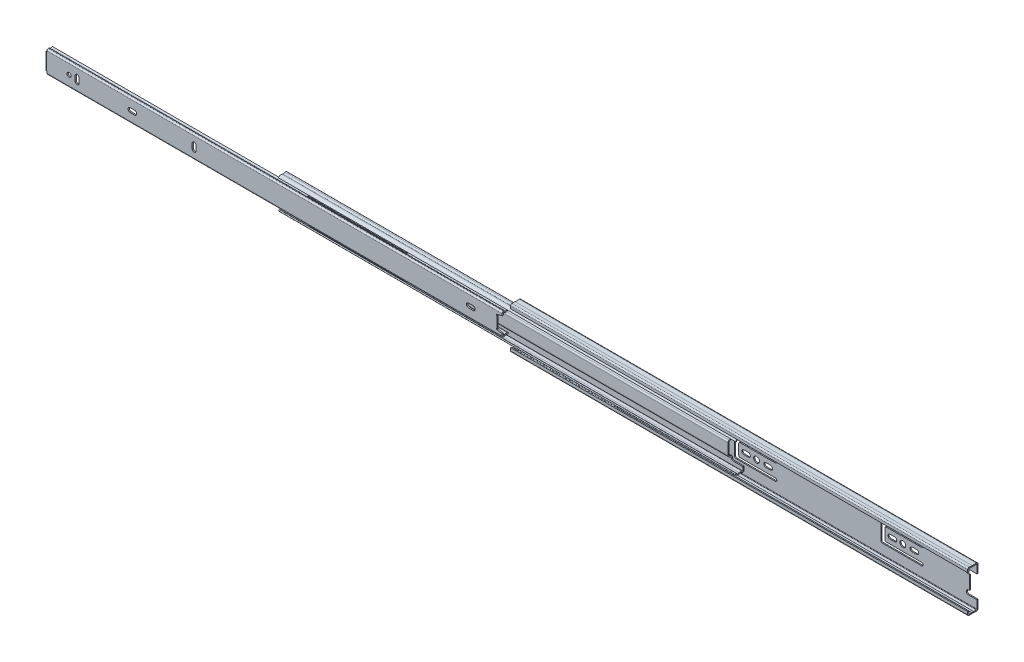
SolidWorks part; units mm, degrees
ref_plane "Front" through (0, 0, 0) normal (0, 0, 1) x (1, 0, 0)
ref_plane "Top" through (0, 0, 0) normal (0, 1, 0) x (1, 0, 0)
ref_plane "Right" through (0, 0, 0) normal (1, 0, 0) x (0, 0, -1)
sketch "Sketch1" plane through (0, 0, 0) normal (1, 0, 0) x (0, 0, -1)
  line L1 (5.6388, 0) -> (-5.6388, 0) construction
  line L4 (-4.1393, 22.8203) -> (-0.7433, 22.6989)
  line L5 (-1.1312, 21.5182) -> (-4.1819, 21.6273)
  line L6 (-4.445, 18.415) -> (-5.6388, 18.415)
  line L7 (-4.445, 21.3734) -> (-4.445, 18.415)
  line L8 (-5.6388, 18.415) -> (-5.6388, 21.3734)
  line L9 (3.9237, 21.6269) -> (0.7619, 21.5441)
  line L10 (5.6388, 0) -> (5.6388, 21.1191)
  line L11 (4.445, 21.1191) -> (4.445, 0)
  line L12 (5.6388, 0) -> (4.445, 0)
  line L13 (-0.7433, 22.6989) -> (3.8925, 22.8203)
  arc A0 (-4.445, 21.3734) -> (-4.1819, 21.6273) centre (-4.191, 21.3734) cw
  arc A1 (-5.6388, 21.3734) -> (-4.1393, 22.8203) centre (-4.191, 21.3734) cw
  arc A3 (3.9237, 21.6269) -> (4.445, 21.1191) centre (3.937, 21.1191) cw
  arc A4 (3.8925, 22.8203) -> (5.6388, 21.1191) centre (3.937, 21.1191) cw
  arc A5 (-1.1312, 21.5182) -> (0.7619, 21.5441) centre (-0.1524, 19.1744) cw
  dimension "D2" = 19.1744
  dimension "D7" = 0.254
  dimension "D8" = 0.508
  dimension "D6" = 2.54
  dimension "D9" = 1.1938
  dimension "D10" = 88.5
  dimension "D1" = 11.2776
  dimension "D3" = 5.7912
  dimension "D4" = 36.83
  dimension "D5" = 1.1938
  dimension "D11" = 87.953
  dimension "D12" = 45.6406
extrude "Extrude1" add sketch "Sketch1" along normal mid plane 500.126
ref_plane "Travel / 2" through (-504.063, 0, 0) normal (-1, 0, 0) x (0, 0, 1)
sketch "Sketch2" plane through (-504.063, 0, 0) normal (-1, 0, 0) x (0, 0, 1)
  line L0 (0.0254, 6.1159) -> (0.0254, 0)
  line L2 (-5.6388, 0) -> (5.6388, 0) construction
  line L3 (5.6388, 21.3734) -> (5.6388, 18.415) construction
  line L7 (-4.445, 21.1191) -> (-4.445, 0) construction
  line L8 (-5.6388, 0) -> (-5.6388, 21.1191) construction
  line L13 (-3.5306, 16.3766) -> (-3.5306, 9.5217)
  line L46 (-2.3867, 7.7262) -> (-0.4146, 6.8065)
  arc A0 (0.0254, 6.1159) -> (-0.4146, 6.8065) centre (-0.7366, 6.1159) ccw
  arc A1 (-1.5056, 17.2916) -> (1.2415, 16.9143) centre (0.1524, 19.1744) ccw
  arc A4 (1.1312, 21.5182) -> (-0.7619, 21.5441) centre (0.1524, 19.1744) ccw construction
  arc A19 (-3.5306, 9.5217) -> (-2.3867, 7.7262) centre (-1.5494, 9.5217) ccw
  arc A25 (-1.5056, 17.2916) -> (-3.5306, 16.3766) centre (-2.3114, 16.3766) ccw
  arc A51 (5.7404, 15.6277) -> (1.2415, 16.9143) centre (2.7686, 13.7451) ccw
  dimension "D2" = 8.4074
  dimension "D3" = 27.4903
  dimension "D6" = 1.9812
  dimension "D8" = 12.2319
  dimension "D10" = 2.5088
  dimension "D11" = 1.2192
  dimension "D4" = 0.762
  dimension "D5" = 4.4704
  dimension "D7" = 115
  dimension "D9" = 19.0435
  dimension "D13" = 11.3792
extrude "Middle Member" add sketch "Sketch2" against normal blind 500.126 separate body thin thin type one direction reverse wall 1.2192
ref_plane "Travel" through (-758.063, 0, 0) normal (-1, 0, 0) x (0, 0, 1)
sketch "Sketch3" plane through (-758.063, 0, 0) normal (-1, 0, 0) x (0, 0, 1)
  line L0 (1.2446, 0) -> (0.0254, 0) construction
  line L1 (-5.6388, 0) -> (-5.6388, 21.1191) construction
  line L56 (7.0612, 0) -> (7.0612, 10.6235)
  line L93 (5.5372, 12.1475) -> (5.1643, 12.1475)
  arc A0 (1.2082, 11.9072) -> (4.2365, 11.8325) centre (2.7686, 13.7451) ccw
  arc A29 (7.0612, 10.6235) -> (5.5372, 12.1475) centre (5.5372, 10.6235) ccw
  arc A53 (5.1643, 12.1475) -> (4.2365, 11.8325) centre (5.1643, 10.6235) ccw
  dimension "D1" = 1.524
  dimension "D4" = 1.524
  dimension "D5" = 2.411
  dimension "D2" = 12.7
  dimension "D3" = 12.1475
  dimension "D6" = 5.853
extrude "Drawer Member" add sketch "Sketch3" against normal blind 500.126 thin thin type one direction wall 1.397
sketch "Sketch6" plane through (0, 0, 7.0612) normal (0, 0, 1) x (1, 0, 0)
  line L1 (-758.063, 0) -> (-756.158, 0)
  line L2 (-758.063, 0) -> (-758.063, 12.1475)
  line L3 (-758.063, 12.1475) -> (-756.158, 12.1475)
  line L4 (-756.158, 0) -> (-756.158, 12.1475)
  line L5 (-257.937, 12.1475) -> (-758.063, 12.1475) construction
  line L7 (-758.063, 10.6235) -> (-758.063, 0) construction
  line L8 (-257.937, 0) -> (-758.063, 0) construction
  dimension "D1" = 1.905
extrude "Cut-Extrude1" cut sketch "Sketch6" against normal through all
sketch "Sketch7" plane through (0, 0, 0) normal (0, -1, 0) x (1, 0, 0)
  line L0 (-756.158, 7.0612) -> (-756.412, 7.0612)
  line L1 (-758.063, 5.4102) -> (-758.063, 0.3041)
  line L2 (-758.063, 0.3041) -> (-756.666, 0.3041)
  line L3 (-756.666, 0.3041) -> (-756.666, 5.4102)
  line L4 (-756.412, 5.6642) -> (-756.158, 5.6642)
  line L5 (-257.937, 5.6642) -> (-756.158, 5.6642) construction
  line L6 (-756.158, 7.0612) -> (-756.158, 5.6642)
  line L7 (-257.937, 0.3041) -> (-756.158, 0.3041) construction
  line L9 (-756.158, 5.087) -> (-756.158, 0.3041) construction
  arc A0 (-756.412, 5.6642) -> (-756.666, 5.4102) centre (-756.412, 5.4102) ccw
  arc A1 (-756.412, 7.0612) -> (-758.063, 5.4102) centre (-756.412, 5.4102) ccw
  dimension "D1" = 0.254
  dimension "D2" = 1.905
extrude "Extrude4" add sketch "Sketch7" against normal blind 8.89
sketch "Sketch8" plane through (0, 0, -4.445) normal (0, 0, 1) x (1, 0, 0)
  line L0 (240.4245, 7.6456) -> (241.8588, 7.493)
  line L1 (250.063, 12.2048) -> (240.6664, 12.2048)
  line L2 (241.8588, 7.493) -> (241.8588, 0)
  line L3 (250.063, 0) -> (-250.063, 0) construction
  line L4 (250.063, 21.1191) -> (250.063, 0) construction
  line L5 (250.063, 12.2048) -> (250.063, 0)
  line L6 (250.063, 0) -> (241.8588, 0)
  arc A0 (240.6664, 12.2048) -> (240.4245, 7.6456) centre (240.6664, 9.9188) ccw
  dimension "D3" = 9.9188
  dimension "D1" = 12.2048
  dimension "D2" = 8.2042
  dimension "D4" = 9.3966
  dimension "D5" = 7.493
extrude "Cut-Extrude2" cut sketch "Sketch8" against normal up to next (1.1938 mm away)
sketch "Sketch11" plane through (0, 0, 7.0612) normal (0, 0, 1) x (1, 0, 0)
  line L0 (-263.652, 5.9678) -> (-263.652, 0)
  line L8 (-257.937, 8.5893) -> (-263.7963, 7.2212)
  line L11 (-263.652, 0) -> (-257.937, 0)
  line L12 (-257.937, 0) -> (-257.937, 8.5893)
  arc A1 (-263.7963, 7.2212) -> (-263.652, 5.9678) centre (-263.6519, 6.6028) ccw
  dimension "D3" = 0.635
  dimension "D1" = 5.715
  dimension "D2" = 8.5893
  dimension "D4" = 5.9678
  dimension "D5" = 103.143
extrude "Cut-Extrude3" cut sketch "Sketch11" against normal up to next (1.397 mm away)
sketch "Sketch12" plane through (0, 0, 1.2446) normal (0, 0, 1) x (1, 0, 0)
  line L0 (-3.937, 12.065) -> (-14.097, 12.065)
  line L1 (-3.937, 16.3766) -> (-3.937, 9.5217) construction
  line L2 (-16.637, 9.525) -> (-16.637, 0)
  line L3 (-3.937, 0) -> (-504.063, 0) construction
  line L4 (-16.637, 0) -> (-3.937, 0)
  line L5 (-3.937, 0) -> (-3.937, 12.065)
  arc A0 (-14.097, 12.065) -> (-16.637, 9.525) centre (-14.097, 9.525) ccw
  point P11 (-16.637, 12.065)
  dimension "D3" = 2.54
  dimension "D1" = 12.7
  dimension "D2" = 12.065
extrude "Cut-Extrude4" cut sketch "Sketch12" against normal through all
sketch "Sketch13" plane through (0, 0, -4.445) normal (0, 0, 1) x (1, 0, 0)
  line L0 (-181.6747, 7.112) -> (-206.5032, 7.112)
  line L1 (241.8588, 0) -> (-250.063, 0) construction
  line L2 (-189.7646, 0) -> (-189.7646, 4.2392) construction
  line L3 (-232.6017, 10.287) -> (-181.6747, 10.287)
  line L4 (-250.063, 21.1191) -> (-250.063, 0) construction
  line L5 (-210.3132, 7.112) -> (-232.6017, 7.112)
  line L6 (-209.5512, 0) -> (-209.5512, 6.35)
  line L7 (-207.2652, 6.35) -> (-207.2652, 0)
  line L8 (-187.2881, 2.286) -> (-192.2411, 2.286)
  line L13 (-226.3406, 0) -> (-221.7686, 0)
  line L14 (-218.238, 0) -> (-211.888, 0)
  line L15 (-209.5512, 0) -> (-207.2652, 0)
  line L16 (-204.7506, 0) -> (-200.1786, 0)
  line L17 (-194.5271, 0) -> (-185.0021, 0)
  arc A1 (-232.6017, 10.287) -> (-232.6017, 7.112) centre (-232.6017, 8.6995) ccw
  arc A2 (-209.5512, 6.35) -> (-210.3132, 7.112) centre (-210.3132, 6.35) ccw
  arc A4 (-206.5032, 7.112) -> (-207.2652, 6.35) centre (-206.5032, 6.35) ccw
  arc A7 (-181.6747, 7.112) -> (-181.6747, 10.287) centre (-181.6747, 8.6995) ccw
  arc A8 (-211.888, 0) -> (-218.238, 0) centre (-215.063, 0) ccw
  arc A9 (-221.7686, 0) -> (-226.3406, 0) centre (-224.0546, 0) ccw
  arc A10 (-200.1786, 0) -> (-204.7506, 0) centre (-202.4646, 0) ccw
  arc A11 (-185.0021, 0) -> (-187.2881, 2.286) centre (-187.2881, 0) ccw
  arc A12 (-192.2411, 2.286) -> (-194.5271, 0) centre (-192.2411, 0) ccw
  dimension "D3" = 2.286
  dimension "D4" = 3.175
  dimension "D7" = 8.9916
  dimension "D8" = 21.59
  dimension "D9" = 34.29
  dimension "D10" = 0.762
  dimension "D11" = 17.5387
  dimension "D12" = 9.525
  dimension "D13" = 5.5118
  dimension "D14" = 35
  dimension "D1" = 3.175
  dimension "D2" = 50.927
  dimension "D5" = 2.286
  dimension "D6" = 10.287
extrude "Cut-Extrude5" cut sketch "Sketch13" against normal up to next (1.1938 mm away)
sketch "Sketch32" plane through (0, 0, -5.6388) normal (0, 0, -1) x (-1, 0, 0)
  line L0 (69.6005, 0) -> (79.1255, 0)
  line L1 (83.888, 0) -> (90.238, 0)
  line L2 (93.7305, 0) -> (103.2555, 0)
  line L3 (106.621, 0) -> (111.193, 0)
  line L4 (-241.8588, 0) -> (185.0021, 0) construction
  line L5 (232.6017, 10.287) -> (181.6747, 10.287) construction
  line L6 (181.6747, 7.112) -> (206.5032, 7.112) construction
  line L7 (98.493, 2.286) -> (98.493, -3.4269) construction
  line L8 (74.363, 2.286) -> (74.363, -3.4269) construction
  line L14 (66.4255, 10.287) -> (109.669, 10.287)
  line L15 (105.097, 7.112) -> (66.4255, 7.112)
  line L17 (111.193, 8.763) -> (111.193, 0)
  line L18 (106.621, 0) -> (106.621, 5.588)
  line L23 (71.8865, 2.286) -> (76.8395, 2.286)
  line L25 (96.0165, 2.286) -> (100.9695, 2.286)
  arc A0 (218.238, 0) -> (211.888, 0) centre (215.063, 0) ccw construction
  arc A13 (111.193, 8.763) -> (109.669, 10.287) centre (109.669, 8.763) ccw
  arc A14 (106.621, 5.588) -> (105.097, 7.112) centre (105.097, 5.588) ccw
  arc A17 (66.4255, 10.287) -> (66.4255, 7.112) centre (66.4255, 8.6995) ccw
  arc A20 (79.1255, 0) -> (76.8395, 2.286) centre (76.8395, 0) ccw
  arc A21 (71.8865, 2.286) -> (69.6005, 0) centre (71.8865, 0) ccw
  arc A22 (90.238, 0) -> (83.888, 0) centre (87.063, 0) ccw
  arc A24 (103.2555, 0) -> (100.9695, 2.286) centre (100.9695, 0) ccw
  arc A25 (96.0165, 2.286) -> (93.7305, 0) centre (96.0165, 0) ccw
  dimension "D2" = 1.524
  dimension "D3" = 3.175
  dimension "D4" = 9.525
  dimension "D5" = 2.286
  dimension "D6" = 11.43
  dimension "D7" = 12.7
  dimension "D8" = 24.13
  dimension "D9" = 20.6375
  dimension "D10" = 128
  dimension "D1" = 4.572
extrude "Cut-Extrude14" cut sketch "Sketch32" against normal up to next (1.1938 mm away)
sketch "Sketch33" plane through (83.6094, 0.8125, -5.6388) normal (0, 0, -1) x (-1, 0, 0)
  line L0 (57.2099, -0.8125) -> (66.7349, -0.8125)
  line L1 (71.4974, -0.8125) -> (77.8474, -0.8125)
  line L2 (81.3399, -0.8125) -> (90.8649, -0.8125)
  line L3 (94.2304, -0.8125) -> (98.8024, -0.8125)
  line L7 (86.1024, 1.4735) -> (86.1024, -4.2394) construction
  line L8 (61.9724, 1.4735) -> (61.9724, -3.4269) construction
  line L9 (-158.2494, -0.8125) -> (153.2099, -0.8125) construction
  line L10 (193.2784, 9.4745) -> (150.0349, 9.4745) construction
  line L11 (150.0349, 6.2995) -> (188.7064, 6.2995) construction
  line L14 (54.0349, 9.4745) -> (97.2784, 9.4745)
  line L15 (92.7064, 6.2995) -> (54.0349, 6.2995)
  line L17 (98.8024, 7.9505) -> (98.8024, -0.8125)
  line L18 (94.2304, -0.8125) -> (94.2304, 4.7755)
  line L23 (59.4959, 1.4735) -> (64.4489, 1.4735)
  line L25 (83.6259, 1.4735) -> (88.5789, 1.4735)
  arc A1 (301.8474, -0.8125) -> (295.4974, -0.8125) centre (298.6724, -0.8125) ccw construction
  arc A13 (98.8024, 7.9505) -> (97.2784, 9.4745) centre (97.2784, 7.9505) ccw
  arc A14 (94.2304, 4.7755) -> (92.7064, 6.2995) centre (92.7064, 4.7755) ccw
  arc A17 (54.0349, 9.4745) -> (54.0349, 6.2995) centre (54.0349, 7.887) ccw
  arc A20 (66.7349, -0.8125) -> (64.4489, 1.4735) centre (64.4489, -0.8125) ccw
  arc A21 (59.4959, 1.4735) -> (57.2099, -0.8125) centre (59.4959, -0.8125) ccw
  arc A22 (77.8474, -0.8125) -> (71.4974, -0.8125) centre (74.6724, -0.8125) ccw
  arc A24 (90.8649, -0.8125) -> (88.5789, 1.4735) centre (88.5789, -0.8125) ccw
  arc A25 (83.6259, 1.4735) -> (81.3399, -0.8125) centre (83.6259, -0.8125) ccw
  dimension "D2" = 1.524
  dimension "D3" = 3.175
  dimension "D4" = 9.525
  dimension "D5" = 2.286
  dimension "D6" = 11.43
  dimension "D7" = 12.7
  dimension "D8" = 24.13
  dimension "D9" = 20.6375
  dimension "D10" = 224
  dimension "D1" = 4.572
extrude "Cut-Extrude6" cut sketch "Sketch33" against normal up to next (1.1938 mm away)
sketch "Sketch34" plane through (169.8236, 1.4527, -5.6388) normal (0, 0, -1) x (-1, 0, 0)
  line L0 (-16.6239, -1.4527) -> (-7.0989, -1.4527)
  line L1 (-2.3364, -1.4527) -> (4.0136, -1.4527)
  line L2 (7.5061, -1.4527) -> (17.0311, -1.4527)
  line L3 (20.3966, -1.4527) -> (24.9686, -1.4527)
  line L4 (-72.0352, -1.4527) -> (143.4241, -1.4527) construction
  line L7 (12.2686, 0.8333) -> (12.2686, -4.8796) construction
  line L8 (-11.8614, 0.8333) -> (-11.8614, -4.0671) construction
  line L9 (279.4926, 8.8343) -> (236.2491, 8.8343) construction
  line L10 (236.2491, 5.6593) -> (274.9206, 5.6593) construction
  line L14 (-19.7989, 8.8343) -> (23.4446, 8.8343)
  line L15 (18.8726, 5.6593) -> (-19.7989, 5.6593)
  line L17 (24.9686, 7.3103) -> (24.9686, -1.4527)
  line L18 (20.3966, -1.4527) -> (20.3966, 4.1353)
  line L23 (-14.3379, 0.8333) -> (-9.3849, 0.8333)
  line L25 (9.7921, 0.8333) -> (14.7451, 0.8333)
  arc A0 (388.0616, -1.4527) -> (381.7116, -1.4527) centre (384.8866, -1.4527) ccw construction
  arc A13 (24.9686, 7.3103) -> (23.4446, 8.8343) centre (23.4446, 7.3103) ccw
  arc A14 (20.3966, 4.1353) -> (18.8726, 5.6593) centre (18.8726, 4.1353) ccw
  arc A17 (-19.7989, 8.8343) -> (-19.7989, 5.6593) centre (-19.7989, 7.2468) ccw
  arc A20 (-7.0989, -1.4527) -> (-9.3849, 0.8333) centre (-9.3849, -1.4527) ccw
  arc A21 (-14.3379, 0.8333) -> (-16.6239, -1.4527) centre (-14.3379, -1.4527) ccw
  arc A22 (4.0136, -1.4527) -> (-2.3364, -1.4527) centre (0.8386, -1.4527) ccw
  arc A24 (17.0311, -1.4527) -> (14.7451, 0.8333) centre (14.7451, -1.4527) ccw
  arc A25 (9.7921, 0.8333) -> (7.5061, -1.4527) centre (9.7921, -1.4527) ccw
  dimension "D2" = 1.524
  dimension "D3" = 3.175
  dimension "D4" = 9.525
  dimension "D5" = 2.286
  dimension "D6" = 11.43
  dimension "D7" = 12.7
  dimension "D8" = 24.13
  dimension "D9" = 20.6375
  dimension "D10" = 384.048
  dimension "D1" = 4.572
extrude "Cut E" cut sketch "Sketch34" against normal up to next (1.1938 mm away)
sketch "Sketch24" plane through (0, 0, 7.0612) normal (0, 0, 1) x (1, 0, 0)
  line L0 (-263.652, 0) -> (-756.412, 0) construction
  line L1 (-723.011, 4.826) -> (-723.011, 0) construction
  line L2 (-725.1954, 2.6416) -> (-725.1954, 0)
  line L3 (-725.1954, 0) -> (-720.8266, 0)
  line L4 (-720.8266, 0) -> (-720.8266, 2.6416)
  line L5 (-667.3215, 0) -> (-657.7965, 0)
  line L6 (-665.0355, 2.286) -> (-660.0825, 2.286)
  line L8 (-597.1954, 2.6416) -> (-597.1954, 0)
  line L9 (-597.1954, 0) -> (-592.8266, 0)
  line L10 (-592.8266, 0) -> (-592.8266, 2.6416)
  line L11 (-758.063, 8.89) -> (-758.063, 0) construction
  line L12 (-662.559, 2.286) -> (-662.559, 0) construction
  circle A0 centre (-731.901, 0) radius 2.1844
  arc A1 (-725.1954, 2.6416) -> (-720.8266, 2.6416) centre (-723.011, 2.6416) cw
  arc A2 (-667.3215, 0) -> (-665.0355, 2.286) centre (-665.0355, 0) cw
  arc A3 (-660.0825, 2.286) -> (-657.7965, 0) centre (-660.0825, 0) cw
  arc A4 (-597.1954, 2.6416) -> (-592.8266, 2.6416) centre (-595.011, 2.6416) cw
  dimension "D1" = 4.3688
  dimension "D4" = 8.89
  dimension "D5" = 2.286
  dimension "D7" = 60.452
  dimension "D8" = 128
  dimension "D2" = 35.052
  dimension "D3" = 4.826
  dimension "D6" = 9.525
extrude "Cut-Extrude13" cut sketch "Sketch24" against normal up to next (1.397 mm away)
sketch "Sketch25" plane through (0, 0, 7.0612) normal (0, 0, 1) x (1, 0, 0)
  line L1 (-263.652, 0) -> (-592.8266, 0) construction
  line L5 (-287.4645, 0) -> (-296.9895, 0)
  line L6 (-660.0825, 2.286) -> (-665.0355, 2.286) construction
  line L7 (-294.7035, 2.286) -> (-289.7505, 2.286)
  line L8 (-292.227, 0) -> (-292.227, 2.286) construction
  arc A1 (-720.8266, 2.6416) -> (-725.1954, 2.6416) centre (-723.011, 2.6416) ccw construction
  arc A3 (-294.7035, 2.286) -> (-296.9895, 0) centre (-294.7035, 0) ccw
  arc A4 (-289.7505, 2.286) -> (-287.4645, 0) centre (-289.7505, 0) cw
  arc A5 (-657.7965, 0) -> (-660.0825, 2.286) centre (-660.0825, 0) ccw construction
  dimension "D1" = 430.784
extrude "Cut D" cut sketch "Sketch25" against normal up to next (1.397 mm away)
sketch "Sketch36" plane through (0, 0, 7.0612) normal (0, 0, 1) x (1, 0, 0)
  line L0 (-309.1954, 0) -> (-304.8266, 0)
  line L1 (-304.8266, 0) -> (-304.8266, 2.6416)
  line L2 (-309.1954, 2.6416) -> (-309.1954, 0)
  line L4 (-296.9895, 0) -> (-592.8266, 0) construction
  line L5 (-720.8266, 0) -> (-720.8266, 2.6416) construction
  arc A0 (-304.8266, 2.6416) -> (-309.1954, 2.6416) centre (-307.011, 2.6416) ccw
  circle A1 centre (-319.711, 0) radius 2.1844
  arc A5 (-720.8266, 2.6416) -> (-725.1954, 2.6416) centre (-723.011, 2.6416) ccw construction
  dimension "D1" = 4.3688
  dimension "D2" = 416
  dimension "D3" = 12.7
extrude "Cut B" [suppressed] cut sketch "Sketch36" against normal up to next
sketch "Sketch38" plane through (0, 0, 7.0612) normal (0, 0, 1) x (1, 0, 0)
  line L0 (-501.1954, 0) -> (-501.1954, 2.6416)
  line L1 (-296.9895, 0) -> (-592.8266, 0) construction
  line L2 (-496.8266, 2.6416) -> (-496.8266, 0)
  line L3 (-496.8266, 0) -> (-501.1954, 0)
  line L4 (-720.8266, 0) -> (-720.8266, 2.6416) construction
  line L5 (-492.28, 0) -> (-484.406, 0)
  line L6 (-492.28, 0) -> (-492.28, 2.3749)
  line L7 (-492.28, 2.3749) -> (-484.406, 2.3749)
  line L8 (-484.406, 0) -> (-484.406, 2.3749)
  line L9 (-499.011, 7.182) -> (-499.011, -4.0911) construction
  line L10 (-505.742, 0) -> (-513.616, 0)
  line L11 (-505.742, 0) -> (-505.742, 2.3749)
  line L12 (-505.742, 2.3749) -> (-513.616, 2.3749)
  line L13 (-513.616, 0) -> (-513.616, 2.3749)
  line L14 (-488.343, 2.3749) -> (-488.343, -3.2385) construction
  arc A0 (-501.1954, 2.6416) -> (-496.8266, 2.6416) centre (-499.011, 2.6416) cw
  arc A1 (-720.8266, 2.6416) -> (-725.1954, 2.6416) centre (-723.011, 2.6416) ccw construction
  dimension "D4" = 224
  dimension "D1" = 7.874
  dimension "D2" = 2.3749
  dimension "D3" = 10.668
extrude "Cut A" [suppressed] cut sketch "Sketch38" against normal up to next
ref_plane "Plane3" through (-237.363, 0, 0) normal (-1, 0, 0) x (0, 0, 1)
sketch "Sketch27" plane through (-237.363, 0, 0) normal (-1, 0, 0) x (0, 0, 1)
  line L0 (0.1524, 21.6832) -> (0.1524, 16.6656)
  line L1 (0.1524, 23.635) -> (0.1524, 15.2838) construction
  arc A0 (0.1524, 16.6656) -> (0.1524, 21.6832) centre (0.1524, 19.1744) ccw
  arc A1 (-1.5056, 17.2916) -> (1.2415, 16.9143) centre (0.1524, 19.1744) ccw construction
revolve "Revolve1" add sketch "Sketch27" angle 360 about L1
pattern_linear "LPattern1" count 6 spacing 19.05 along (1, 0, 0) of bodies 128
sketch "Sketch28" plane through (-237.363, 0, 0) normal (-1, 0, 0) x (0, 0, 1)
  line L0 (2.6612, 19.1744) -> (-2.3564, 19.1744) construction
  line L1 (3.9624, 18.7934) -> (-3.6576, 18.7934)
  line L2 (3.9624, 18.7934) -> (3.9624, 19.5554)
  line L3 (3.9624, 19.5554) -> (-3.6576, 19.5554)
  line L4 (-3.6576, 18.7934) -> (-3.6576, 19.5554)
  line L5 (0.1524, 20.5465) -> (0.1524, 17.804) construction
  circle A1 centre (0.1524, 19.1744) radius 2.5088 construction
  point P8 (0.1524, 19.1744)
  dimension "D1" = 7.62
  dimension "D2" = 0.762
extrude "Extrude7" add sketch "Sketch28" along normal blind 6.35 and the other way blind 101.6
ref_plane "Plane4" through (-465.963, 0, 0) normal (-1, 0, 0) x (0, 0, 1)
sketch "Sketch29" plane through (-465.963, 0, 0) normal (-1, 0, 0) x (0, 0, 1)
  line L0 (2.7686, 16.0438) -> (2.7686, 11.4464)
  line L1 (2.7686, 16.6801) -> (2.7686, 10.2973) construction
  arc A0 (2.7686, 11.4464) -> (2.7686, 16.0438) centre (2.7686, 13.7451) ccw
  arc A1 (4.7105, 14.9753) -> (1.7707, 15.816) centre (2.7686, 13.7451) ccw construction
revolve "Revolve2" add sketch "Sketch29" angle 360 about L1
pattern_linear "LPattern2" count 6 spacing 19.05 along (1, 0, 0) of bodies 135
sketch "Sketch30" plane through (-465.963, 0, 0) normal (-1, 0, 0) x (0, 0, 1)
  line L0 (0.4699, 13.7451) -> (5.0673, 13.7451) construction
  line L1 (3.9624, 18.7934) -> (3.9624, 19.5554) construction
  line L2 (0.2286, 14.1261) -> (5.3086, 14.1261)
  line L3 (0.2286, 14.1261) -> (0.2286, 13.3641)
  line L4 (0.2286, 13.3641) -> (5.3086, 13.3641)
  line L5 (5.3086, 14.1261) -> (5.3086, 13.3641)
  line L7 (2.7686, 14.2437) -> (2.7686, 12.7853) construction
  circle A0 centre (2.7686, 13.7451) radius 2.2987 construction
  point P4 (2.7686, 13.7451)
  dimension "D1" = 5.08
extrude "Extrude8" add sketch "Sketch30" along normal blind 6.35 and the other way blind 101.6
mirror "Mirror3" about plane through (0, 0, 0) normal (0, 1, 0) of bodies 126 119 164 117 124 127 159
mirror "Mirror5" about plane through (0, 0, 0) normal (0, 1, 0) of bodies 141 134
sketch "Sketch40" plane through (0, 0, 7.0612) normal (0, 0, 1) x (1, 0, 0)
  line L0 (-595.011, -4.826) -> (-595.011, 0) construction
  arc A0 (-597.1954, -2.6416) -> (-592.8266, -2.6416) centre (-595.011, -2.6416) ccw construction
sketch "Sketch41" plane through (0, 0, -5.6388) normal (0, 0, -1) x (-1, 0, 0)
  line L0 (-168.985, 3.175) -> (-168.985, -3.175) construction
  line L1 (-8.937, 3.175) -> (-8.937, -3.175) construction
  line L2 (87.063, -3.175) -> (87.063, 3.175) construction
  circle A0 centre (-168.985, 0) radius 3.175 construction
  circle A1 centre (-8.937, 0) radius 3.175 construction
  circle A2 centre (87.063, 0) radius 3.175 construction
